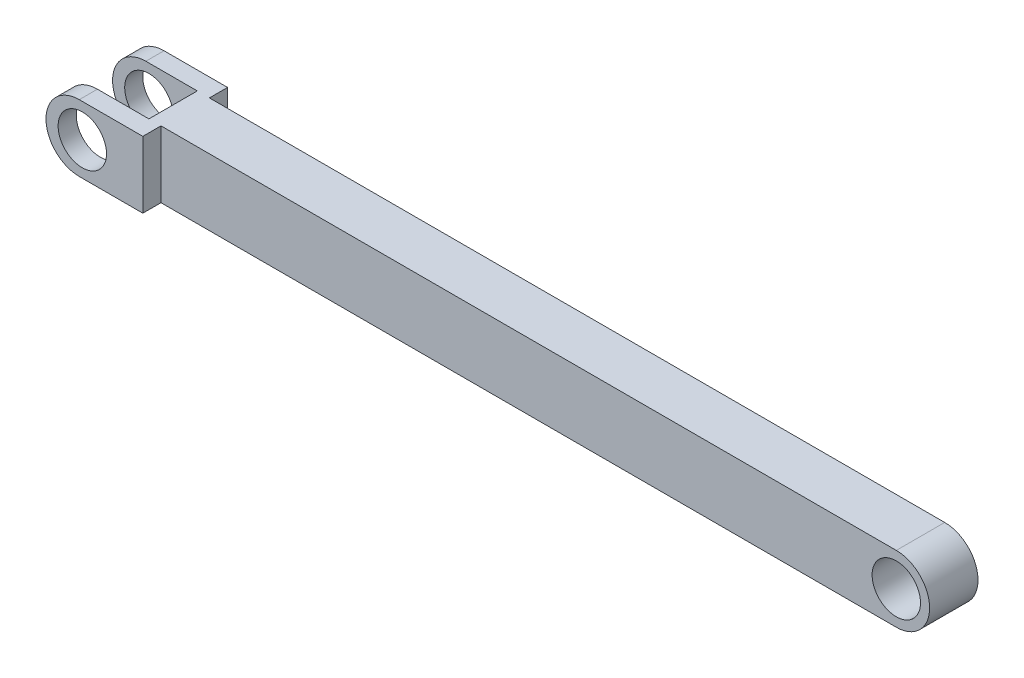
SolidWorks part; units mm, degrees
ref_plane "Front Plane" through (0, 0, 0) normal (0, 0, 1) x (1, 0, 0)
ref_plane "Top Plane" through (0, 0, 0) normal (0, 1, 0) x (1, 0, 0)
ref_plane "Right Plane" through (0, 0, 0) normal (1, 0, 0) x (0, 0, -1)
sketch "Sketch1" plane through (0, 0, 0) normal (0, 0, 1) x (1, 0, 0)
  line L0 (0, 0) -> (-65.75, 0) construction
  line L1 (0, 2.75) -> (-60.75, 2.75)
  line L2 (-60.75, 2.75) -> (-60.75, -2.75)
  line L3 (-60.75, -2.75) -> (0, -2.75)
  circle A0 centre (0, 0) radius 2
  arc A1 (0, 2.75) -> (0, -2.75) centre (0, 0) cw
  dimension "D1" = 4
  dimension "D3" = 2.75
  dimension "D4" = 60.75
  dimension "D2" = 65.75
extrude "Boss-Extrude1" add sketch "Sketch1" along normal blind 4
ref_plane "Plane1" through (-60.75, 0, 0) normal (-1, 0, 0) x (0, 0, 1)
sketch "Sketch2" plane through (-60.75, 0, 0) normal (-1, 0, 0) x (0, 0, 1)
  line L0 (2, -2.75) -> (2, 2.75) construction
  line L1 (-1.5, 2.75) -> (5.5, 2.75)
  line L2 (-1.5, 2.75) -> (-1.5, -2.75)
  line L3 (-1.5, -2.75) -> (5.5, -2.75)
  line L4 (5.5, 2.75) -> (5.5, -2.75)
  line L5 (4, -2.75) -> (0, -2.75) construction
  point P8 (2, 0)
  dimension "D1" = 3.5
  dimension "D2" = 7
  dimension "D3" = 2.75
  dimension "D4" = 5.5
extrude "Boss-Extrude2" add sketch "Sketch2" along normal blind 8
sketch "Sketch4" plane through (0, 0, 0) normal (0, 1, 0) x (1, 0, 0)
  line L0 (-68.75, -2) -> (-60.75, -2) construction
  line L1 (-68.75, -5.5) -> (-68.75, 1.5) construction
  line L2 (-60.75, 55) -> (-60.75, -55) construction
  line L4 (-68.75, 0) -> (-61.75, 0)
  line L5 (-68.75, 0) -> (-68.75, -4)
  line L6 (-68.75, -4) -> (-61.75, -4)
  line L7 (-61.75, 0) -> (-61.75, -4)
  dimension "D1" = 1
  dimension "D2" = 2
  dimension "D3" = 4
extrude "Cut-Extrude1" cut sketch "Sketch4" against normal through all both and the other way through all
sketch "Sketch5" plane through (0, 0, 0) normal (0, 0, 1) x (1, 0, 0)
  line L0 (-60.75, 55) -> (-60.75, -55) construction
  line L1 (-68.75, 2.75) -> (-60.75, 2.75) construction
  circle A0 centre (-65.75, 0) radius 2
  dimension "D1" = 4
  dimension "D2" = 5
  dimension "D3" = 2.75
extrude "Cut-Extrude2" cut sketch "Sketch5" against normal through all both and the other way through all
fillet "Fillet1" radius 2.75 4 edges at (-68.75, -2.75, 4.75) (-68.75, -2.75, -0.75) (-68.75, 2.75, -0.75) (-68.75, 2.75, 4.75)
